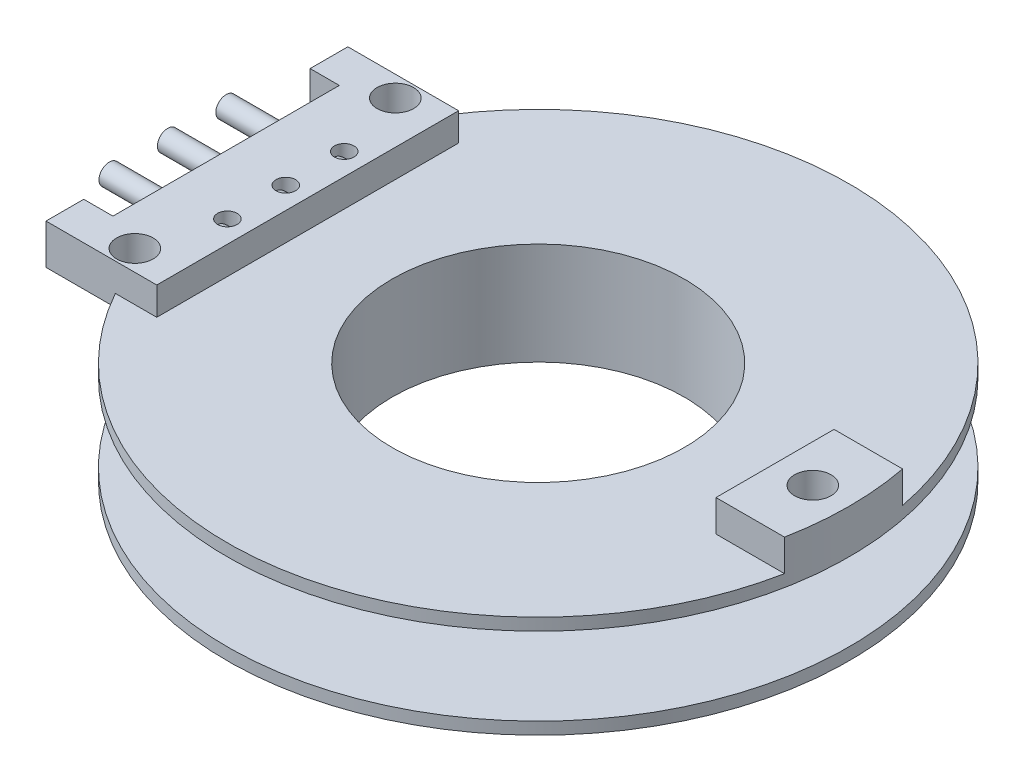
SolidWorks part; units mm, degrees
material "Полиамид ПА-6Б ТУ 6-05-988-93"
ref_plane "Спереди" through (0, 0, 0) normal (0, 0, 1) x (1, 0, 0)
ref_plane "Сверху" through (0, 0, 0) normal (0, 1, 0) x (1, 0, 0)
ref_plane "Справа" through (0, 0, 0) normal (1, 0, 0) x (0, 0, -1)
sketch "Эскиз1" plane through (0, 0, 0) normal (0, 0, 1) x (1, 0, 0)
  line L0 (7, 1.6) -> (7, -1.6)
  line L1 (7, -1.6) -> (12.775, -1.6)
  line L2 (12.775, -1.6) -> (12.775, -2.1)
  line L3 (12.775, -2.1) -> (6, -2.1)
  line L4 (6, -2.1) -> (6, 2.1)
  line L5 (6, 2.1) -> (12.775, 2.1)
  line L6 (12.775, 2.1) -> (12.775, 1.6)
  line L7 (12.775, 1.6) -> (7, 1.6)
  line L8 (6, 0) -> (0, 0) construction
  line L9 (0, 2.1) -> (0, -2.1) construction
  dimension "D1" = 6
  dimension "D2" = 0.5
  dimension "D3" = 1
  dimension "D4" = 4.2
  dimension "D5" = 12.775
revolve "Повернуть1" add sketch "Эскиз1" angle 360 about L9
sketch "Эскиз2" plane through (0, 2.1, 0) normal (0, 1, 0) x (1, 0, 0)
  line L0 (9.7273, 2.425) -> (12.5427, 2.425)
  line L1 (9.7273, -2.425) -> (12.5427, -2.425)
  line L2 (10.025, 0) -> (0, 0) construction
  line L3 (9.7273, 2.425) -> (9.7273, -2.425)
  circle A0 centre (0, 0) radius 12.775 construction
  arc A1 (12.5427, -2.425) -> (12.5427, 2.425) centre (0, 0) ccw
  arc A2 (9.7273, -2.425) -> (9.7273, 2.425) centre (0, 0) ccw construction
  dimension "D1" = 2.75
  dimension "D2" = 4.85
extrude "Бобышка-Вытянуть1" add sketch "Эскиз2" along normal blind 1.3
sketch "Эскиз3" plane through (0, 2.1, 0) normal (0, 1, 0) x (1, 0, 0)
  line L0 (-14.02, 6.2) -> (-9.47, 6.2)
  line L1 (-9.47, 6.2) -> (-9.47, -6.2)
  line L2 (-9.47, -6.2) -> (-14.02, -6.2)
  line L3 (-14.02, -6.2) -> (-14.02, -4.65)
  line L4 (-14.02, -4.65) -> (-12.82, -4.65)
  line L5 (-12.82, -4.65) -> (-12.82, 4.65)
  line L6 (-12.82, 4.65) -> (-14.02, 4.65)
  line L7 (-14.02, 4.65) -> (-14.02, 6.2)
  line L8 (-9.47, 0) -> (0, 0) construction
  line L9 (9.7273, 2.425) -> (9.7273, -2.425) construction
  dimension "D1" = 4.55
  dimension "D2" = 12.4
  dimension "D3" = 1.55
  dimension "D4" = 3.35
  dimension "D5" = 9.47
  dimension "D7" = 9.7273
extrude "Бобышка-Вытянуть2" add sketch "Эскиз3" along normal blind 1.15 and the other way blind 0.5
sketch "Эскиз4" plane through (0, 3.25, 0) normal (0, 1, 0) x (1, 0, 0)
  line L0 (-11.22, 5.35) -> (-11.22, -5.35) construction
  line L1 (-11.22, 0) -> (0, 0) construction
  line L2 (-9.47, 6.2) -> (-9.47, -6.2) construction
  circle A0 centre (-11.22, 5.35) radius 0.75
  circle A1 centre (-11.22, -5.35) radius 0.75
  dimension "D1" = 1.5
  dimension "D2" = 10.7
  dimension "D3" = 1.75
extrude "Вырез-Вытянуть1" cut sketch "Эскиз4" against normal up to surface (1.65 mm away) up to face at (-10.0143, 1.6, 0)
sketch "Эскиз5" plane through (0, 3.25, 0) normal (0, 1, 0) x (1, 0, 0)
  line L0 (-9.47, -6.2) -> (-9.47, 6.2) construction
  circle A0 centre (-10.37, 2.4) radius 0.4
  circle A1 centre (-10.37, 0) radius 0.4
  circle A2 centre (-10.37, -2.4) radius 0.4
  dimension "D2" = 0.8
  dimension "D1" = 0.9
  dimension "D3" = 2.4
  dimension "D4" = 2.4
extrude "Вырез-Вытянуть2" cut sketch "Эскиз5" against normal blind 1.55
sketch "Эскиз6" plane through (-12.82, 0, 0) normal (-1, 0, 0) x (0, 0, 1)
  line L0 (-2.4, 2.425) -> (-4.65, 2.425) construction
  line L1 (-4.65, 1.6) -> (-4.65, 3.25) construction
  circle A0 centre (0, 2.425) radius 0.425
  circle A1 centre (2.4, 2.425) radius 0.425
  circle A2 centre (-2.4, 2.425) radius 0.425
  dimension "D3" = 0.85
  dimension "D1" = 2.4
  dimension "D2" = 2.4
extrude "Бобышка-Вытянуть3" add sketch "Эскиз6" along normal blind 2.4 and the other way blind 3 separate body
sketch "Эскиз7" plane through (0, 3.4, 0) normal (0, 1, 0) x (1, 0, 0)
  circle A0 centre (11.28, 0) radius 0.75
  circle A1 centre (-11.22, 5.35) radius 0.75 construction
  dimension "D1" = 11.28
extrude "Вырез-Вытянуть3" cut sketch "Эскиз7" against normal up to surface (1.8 mm away) up to face at (-11.97, 1.6, 5.35)
